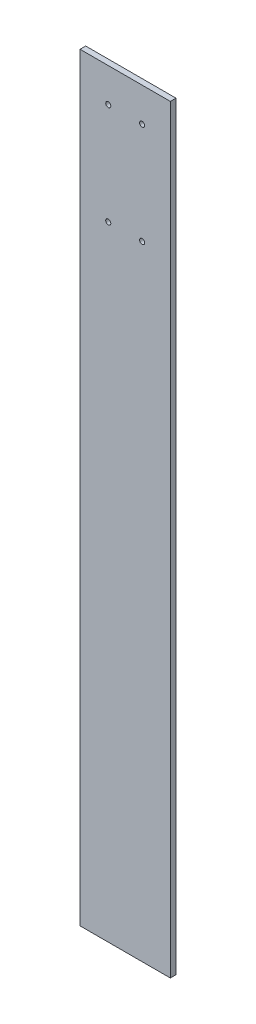
SolidWorks part; units mm, degrees
material "Acrylic (Medium-high impact)"
ref_plane "Front Plane" through (0, 0, 0) normal (0, 0, 1) x (1, 0, 0)
ref_plane "Top Plane" through (0, 0, 0) normal (0, 1, 0) x (1, 0, 0)
ref_plane "Right Plane" through (0, 0, 0) normal (1, 0, 0) x (0, 0, -1)
sketch "Sketch1" plane through (0, 0, 0) normal (0, 1, 0) x (1, 0, 0)
  line L0 (0, 0) -> (0, 76.2) construction
  line L2 (25.4, 68.667) -> (-25.4, 68.667)
  line L3 (25.4, 68.667) -> (25.4, 71.842)
  line L4 (25.4, 71.842) -> (-25.4, 71.842)
  line L5 (-25.4, 68.667) -> (-25.4, 71.842)
  line L6 (25.4, 68.667) -> (-25.4, 71.842) construction
  line L7 (25.4, 71.842) -> (-25.4, 68.667) construction
  circle A0 centre (0, 0) radius 76.2 construction
  point P4 (0, 70.2545)
  dimension "D1" = 152.4
  dimension "D2" = 3.175
  dimension "D3" = 50.8
extrude "Boss-Extrude1" add sketch "Sketch1" along normal blind 427.1518
sketch "Sketch2" plane through (0, 0, -68.667) normal (0, 0, 1) x (1, 0, 0)
  line L1 (-25.4, 427.1518) -> (25.4, 427.1518)
  line L2 (-25.4, 427.1518) -> (-25.4, 0)
  line L3 (-25.4, 0) -> (25.4, 0)
  line L4 (25.4, 427.1518) -> (25.4, 0)
sketch "Sketch3" plane through (0, 0, -68.667) normal (0, 0, 1) x (1, 0, 0)
  line L0 (0, 427.1518) -> (0, 0) construction
  line L1 (-25.4, 427.1518) -> (25.4, 427.1518) construction
  line L2 (-25.4, 0) -> (25.4, 0) construction
  line L3 (-25.4, 213.5759) -> (25.4, 213.5759) construction
  line L4 (-25.4, 427.1518) -> (-25.4, 0) construction
  line L5 (25.4, 427.1518) -> (25.4, 0) construction
  circle A0 centre (-19.05, 376.3518) radius 1.4224
  circle A1 centre (-12.7, 376.3518) radius 1.4224
  circle A2 centre (-6.35, 376.3518) radius 1.4224
  circle A3 centre (0, 376.3518) radius 1.4224
  circle A4 centre (6.35, 376.3518) radius 1.4224
  circle A5 centre (12.7, 376.3518) radius 1.4224
  circle A6 centre (19.05, 376.3518) radius 1.4224
  circle A7 centre (-12.7, 370.0018) radius 1.4224
  circle A8 centre (-6.35, 370.0018) radius 1.4224
  circle A9 centre (0, 370.0018) radius 1.4224
  circle A10 centre (6.35, 370.0018) radius 1.4224
  circle A11 centre (12.7, 370.0018) radius 1.4224
  circle A12 centre (19.05, 370.0018) radius 1.4224
  circle A13 centre (-12.7, 363.6518) radius 1.4224
  circle A14 centre (-6.35, 363.6518) radius 1.4224
  circle A15 centre (0, 363.6518) radius 1.4224
  circle A16 centre (6.35, 363.6518) radius 1.4224
  circle A17 centre (12.7, 363.6518) radius 1.4224
  circle A18 centre (19.05, 363.6518) radius 1.4224
  circle A19 centre (-12.7, 357.3018) radius 1.4224
  circle A20 centre (-6.35, 357.3018) radius 1.4224
  circle A21 centre (0, 357.3018) radius 1.4224
  circle A22 centre (6.35, 357.3018) radius 1.4224
  circle A23 centre (12.7, 357.3018) radius 1.4224
  circle A24 centre (19.05, 357.3018) radius 1.4224
  circle A25 centre (-12.7, 350.9518) radius 1.4224
  circle A26 centre (-6.35, 350.9518) radius 1.4224
  circle A27 centre (0, 350.9518) radius 1.4224
  circle A28 centre (6.35, 350.9518) radius 1.4224
  circle A29 centre (12.7, 350.9518) radius 1.4224
  circle A30 centre (19.05, 350.9518) radius 1.4224
  circle A31 centre (-12.7, 344.6018) radius 1.4224
  circle A32 centre (-6.35, 344.6018) radius 1.4224
  circle A33 centre (0, 344.6018) radius 1.4224
  circle A34 centre (6.35, 344.6018) radius 1.4224
  circle A35 centre (12.7, 344.6018) radius 1.4224
  circle A36 centre (19.05, 344.6018) radius 1.4224
  circle A37 centre (-12.7, 338.2518) radius 1.4224
  circle A38 centre (-6.35, 338.2518) radius 1.4224
  circle A39 centre (0, 338.2518) radius 1.4224
  circle A40 centre (6.35, 338.2518) radius 1.4224
  circle A41 centre (12.7, 338.2518) radius 1.4224
  circle A42 centre (19.05, 338.2518) radius 1.4224
  circle A43 centre (-12.7, 331.9018) radius 1.4224
  circle A44 centre (-6.35, 331.9018) radius 1.4224
  circle A45 centre (0, 331.9018) radius 1.4224
  circle A46 centre (6.35, 331.9018) radius 1.4224
  circle A47 centre (12.7, 331.9018) radius 1.4224
  circle A48 centre (19.05, 331.9018) radius 1.4224
  circle A49 centre (-19.05, 370.0018) radius 1.4224
  circle A50 centre (-19.05, 363.6518) radius 1.4224
  circle A51 centre (-19.05, 357.3018) radius 1.4224
  circle A52 centre (-19.05, 350.9518) radius 1.4224
  circle A53 centre (-19.05, 344.6018) radius 1.4224
  circle A54 centre (-19.05, 338.2518) radius 1.4224
  circle A55 centre (-19.05, 331.9018) radius 1.4224
  circle A56 centre (-19.05, 325.5518) radius 1.4224
  circle A57 centre (-12.7, 325.5518) radius 1.4224
  circle A58 centre (-6.35, 325.5518) radius 1.4224
  circle A59 centre (0, 325.5518) radius 1.4224
  circle A60 centre (6.35, 325.5518) radius 1.4224
  circle A61 centre (12.7, 325.5518) radius 1.4224
  circle A62 centre (19.05, 325.5518) radius 1.4224
  circle A63 centre (-19.05, 319.2018) radius 1.4224
  circle A64 centre (-12.7, 319.2018) radius 1.4224
  circle A65 centre (-6.35, 319.2018) radius 1.4224
  circle A66 centre (0, 319.2018) radius 1.4224
  circle A67 centre (6.35, 319.2018) radius 1.4224
  circle A68 centre (12.7, 319.2018) radius 1.4224
  circle A69 centre (19.05, 319.2018) radius 1.4224
  circle A70 centre (-19.05, 312.8518) radius 1.4224
  circle A71 centre (-12.7, 312.8518) radius 1.4224
  circle A72 centre (-6.35, 312.8518) radius 1.4224
  circle A73 centre (0, 312.8518) radius 1.4224
  circle A74 centre (6.35, 312.8518) radius 1.4224
  circle A75 centre (12.7, 312.8518) radius 1.4224
  circle A76 centre (19.05, 312.8518) radius 1.4224
  circle A77 centre (-19.05, 306.5018) radius 1.4224
  circle A78 centre (-12.7, 306.5018) radius 1.4224
  circle A79 centre (-6.35, 306.5018) radius 1.4224
  circle A80 centre (0, 306.5018) radius 1.4224
  circle A81 centre (6.35, 306.5018) radius 1.4224
  circle A82 centre (12.7, 306.5018) radius 1.4224
  circle A83 centre (19.05, 306.5018) radius 1.4224
  circle A84 centre (-19.05, 300.1518) radius 1.4224
  circle A85 centre (-12.7, 300.1518) radius 1.4224
  circle A86 centre (-6.35, 300.1518) radius 1.4224
  circle A87 centre (0, 300.1518) radius 1.4224
  circle A88 centre (6.35, 300.1518) radius 1.4224
  circle A89 centre (12.7, 300.1518) radius 1.4224
  circle A90 centre (19.05, 300.1518) radius 1.4224
  circle A91 centre (-19.05, 293.8018) radius 1.4224
  circle A92 centre (-12.7, 293.8018) radius 1.4224
  circle A93 centre (-6.35, 293.8018) radius 1.4224
  circle A94 centre (0, 293.8018) radius 1.4224
  circle A95 centre (6.35, 293.8018) radius 1.4224
  circle A96 centre (12.7, 293.8018) radius 1.4224
  circle A97 centre (19.05, 293.8018) radius 1.4224
  circle A98 centre (-19.05, 287.4518) radius 1.4224
  circle A99 centre (-12.7, 287.4518) radius 1.4224
  circle A100 centre (-6.35, 287.4518) radius 1.4224
  circle A101 centre (0, 287.4518) radius 1.4224
  circle A102 centre (6.35, 287.4518) radius 1.4224
  circle A103 centre (12.7, 287.4518) radius 1.4224
  circle A104 centre (19.05, 287.4518) radius 1.4224
  circle A105 centre (19.05, 139.7) radius 1.4224
  circle A106 centre (12.7, 139.7) radius 1.4224
  circle A107 centre (6.35, 139.7) radius 1.4224
  circle A108 centre (0, 139.7) radius 1.4224
  circle A109 centre (-6.35, 139.7) radius 1.4224
  circle A110 centre (-12.7, 139.7) radius 1.4224
  circle A111 centre (-19.05, 139.7) radius 1.4224
  circle A112 centre (19.05, 133.35) radius 1.4224
  circle A113 centre (12.7, 133.35) radius 1.4224
  circle A114 centre (6.35, 133.35) radius 1.4224
  circle A115 centre (0, 133.35) radius 1.4224
  circle A116 centre (-6.35, 133.35) radius 1.4224
  circle A117 centre (-12.7, 133.35) radius 1.4224
  circle A118 centre (-19.05, 133.35) radius 1.4224
  circle A119 centre (19.05, 127) radius 1.4224
  circle A120 centre (12.7, 127) radius 1.4224
  circle A121 centre (6.35, 127) radius 1.4224
  circle A122 centre (0, 127) radius 1.4224
  circle A123 centre (-6.35, 127) radius 1.4224
  circle A124 centre (-12.7, 127) radius 1.4224
  circle A125 centre (-19.05, 127) radius 1.4224
  circle A126 centre (19.05, 120.65) radius 1.4224
  circle A127 centre (12.7, 120.65) radius 1.4224
  circle A128 centre (6.35, 120.65) radius 1.4224
  circle A129 centre (0, 120.65) radius 1.4224
  circle A130 centre (-6.35, 120.65) radius 1.4224
  circle A131 centre (-12.7, 120.65) radius 1.4224
  circle A132 centre (-19.05, 120.65) radius 1.4224
  circle A133 centre (19.05, 114.3) radius 1.4224
  circle A134 centre (12.7, 114.3) radius 1.4224
  circle A135 centre (6.35, 114.3) radius 1.4224
  circle A136 centre (0, 114.3) radius 1.4224
  circle A137 centre (-6.35, 114.3) radius 1.4224
  circle A138 centre (-12.7, 114.3) radius 1.4224
  circle A139 centre (-19.05, 114.3) radius 1.4224
  circle A140 centre (19.05, 107.95) radius 1.4224
  circle A141 centre (12.7, 107.95) radius 1.4224
  circle A142 centre (6.35, 107.95) radius 1.4224
  circle A143 centre (0, 107.95) radius 1.4224
  circle A144 centre (-6.35, 107.95) radius 1.4224
  circle A145 centre (-12.7, 107.95) radius 1.4224
  circle A146 centre (-19.05, 107.95) radius 1.4224
  circle A147 centre (19.05, 101.6) radius 1.4224
  circle A148 centre (12.7, 101.6) radius 1.4224
  circle A149 centre (6.35, 101.6) radius 1.4224
  circle A150 centre (0, 101.6) radius 1.4224
  circle A151 centre (-6.35, 101.6) radius 1.4224
  circle A152 centre (-12.7, 101.6) radius 1.4224
  circle A153 centre (-19.05, 101.6) radius 1.4224
  circle A154 centre (-19.05, 95.25) radius 1.4224
  circle A155 centre (-19.05, 88.9) radius 1.4224
  circle A156 centre (-19.05, 82.55) radius 1.4224
  circle A157 centre (-19.05, 76.2) radius 1.4224
  circle A158 centre (-19.05, 69.85) radius 1.4224
  circle A159 centre (-19.05, 63.5) radius 1.4224
  circle A160 centre (-19.05, 57.15) radius 1.4224
  circle A161 centre (19.05, 95.25) radius 1.4224
  circle A162 centre (12.7, 95.25) radius 1.4224
  circle A163 centre (6.35, 95.25) radius 1.4224
  circle A164 centre (0, 95.25) radius 1.4224
  circle A165 centre (-6.35, 95.25) radius 1.4224
  circle A166 centre (-12.7, 95.25) radius 1.4224
  circle A167 centre (19.05, 88.9) radius 1.4224
  circle A168 centre (12.7, 88.9) radius 1.4224
  circle A169 centre (6.35, 88.9) radius 1.4224
  circle A170 centre (0, 88.9) radius 1.4224
  circle A171 centre (-6.35, 88.9) radius 1.4224
  circle A172 centre (-12.7, 88.9) radius 1.4224
  circle A173 centre (19.05, 82.55) radius 1.4224
  circle A174 centre (12.7, 82.55) radius 1.4224
  circle A175 centre (6.35, 82.55) radius 1.4224
  circle A176 centre (0, 82.55) radius 1.4224
  circle A177 centre (-6.35, 82.55) radius 1.4224
  circle A178 centre (-12.7, 82.55) radius 1.4224
  circle A179 centre (19.05, 76.2) radius 1.4224
  circle A180 centre (12.7, 76.2) radius 1.4224
  circle A181 centre (6.35, 76.2) radius 1.4224
  circle A182 centre (0, 76.2) radius 1.4224
  circle A183 centre (-6.35, 76.2) radius 1.4224
  circle A184 centre (-12.7, 76.2) radius 1.4224
  circle A185 centre (19.05, 69.85) radius 1.4224
  circle A186 centre (12.7, 69.85) radius 1.4224
  circle A187 centre (6.35, 69.85) radius 1.4224
  circle A188 centre (0, 69.85) radius 1.4224
  circle A189 centre (-6.35, 69.85) radius 1.4224
  circle A190 centre (-12.7, 69.85) radius 1.4224
  circle A191 centre (19.05, 63.5) radius 1.4224
  circle A192 centre (12.7, 63.5) radius 1.4224
  circle A193 centre (6.35, 63.5) radius 1.4224
  circle A194 centre (0, 63.5) radius 1.4224
  circle A195 centre (-6.35, 63.5) radius 1.4224
  circle A196 centre (-12.7, 63.5) radius 1.4224
  circle A197 centre (19.05, 57.15) radius 1.4224
  circle A198 centre (12.7, 57.15) radius 1.4224
  circle A199 centre (6.35, 57.15) radius 1.4224
  circle A200 centre (0, 57.15) radius 1.4224
  circle A201 centre (-6.35, 57.15) radius 1.4224
  circle A202 centre (-12.7, 57.15) radius 1.4224
  circle A203 centre (19.05, 50.8) radius 1.4224
  circle A204 centre (12.7, 50.8) radius 1.4224
  circle A205 centre (6.35, 50.8) radius 1.4224
  circle A206 centre (0, 50.8) radius 1.4224
  circle A207 centre (-6.35, 50.8) radius 1.4224
  circle A208 centre (-12.7, 50.8) radius 1.4224
  circle A209 centre (-19.05, 50.8) radius 1.4224
  dimension "D1" = 2.8448
  dimension "D2" = 6.35
  dimension "D3" = 50.8
  dimension "D4" = 7
  dimension "D5" = 8
  dimension "D6" = 8
sketch "Sketch4" plane through (0, 0, -68.667) normal (0, 0, 1) x (1, 0, 0)
  line L0 (0, 427.1518) -> (0, 0) construction
  line L1 (-25.4, 427.1518) -> (25.4, 427.1518) construction
  line L2 (-25.4, 0) -> (25.4, 0) construction
  circle A0 centre (-3.175, 376.3518) radius 1.4224
  circle A2 centre (-9.525, 376.3518) radius 1.4224
  circle A4 centre (-9.525, 370.0018) radius 1.4224
  circle A6 centre (-9.525, 363.6518) radius 1.4224
  circle A8 centre (-9.525, 357.3018) radius 1.4224
  circle A10 centre (-9.525, 350.9518) radius 1.4224
  circle A12 centre (-9.525, 344.6018) radius 1.4224
  circle A14 centre (-9.525, 338.2518) radius 1.4224
  circle A16 centre (-9.525, 331.9018) radius 1.4224
  circle A18 centre (-9.525, 325.5518) radius 1.4224
  circle A20 centre (-9.525, 319.2018) radius 1.4224
  circle A22 centre (-9.525, 312.8518) radius 1.4224
  circle A24 centre (-9.525, 306.5018) radius 1.4224
  circle A26 centre (-9.525, 300.1518) radius 1.4224
  circle A28 centre (-9.525, 293.8018) radius 1.4224
  circle A30 centre (-9.525, 287.4518) radius 1.4224
  circle A32 centre (-9.525, 281.1018) radius 1.4224
  circle A34 centre (-3.175, 370.0018) radius 1.4224
  circle A35 centre (-3.175, 363.6518) radius 1.4224
  circle A36 centre (-3.175, 357.3018) radius 1.4224
  circle A37 centre (-3.175, 350.9518) radius 1.4224
  circle A38 centre (-3.175, 344.6018) radius 1.4224
  circle A39 centre (-3.175, 338.2518) radius 1.4224
  circle A40 centre (-3.175, 331.9018) radius 1.4224
  circle A41 centre (-3.175, 325.5518) radius 1.4224
  circle A42 centre (-3.175, 319.2018) radius 1.4224
  circle A43 centre (-3.175, 312.8518) radius 1.4224
  circle A44 centre (-3.175, 306.5018) radius 1.4224
  circle A45 centre (-3.175, 300.1518) radius 1.4224
  circle A46 centre (-3.175, 293.8018) radius 1.4224
  circle A47 centre (-3.175, 287.4518) radius 1.4224
  circle A48 centre (-3.175, 281.1018) radius 1.4224
  circle A49 centre (3.175, 281.1018) radius 1.4224
  circle A50 centre (3.175, 287.4518) radius 1.4224
  circle A51 centre (3.175, 293.8018) radius 1.4224
  circle A52 centre (3.175, 300.1518) radius 1.4224
  circle A53 centre (3.175, 306.5018) radius 1.4224
  circle A54 centre (3.175, 312.8518) radius 1.4224
  circle A55 centre (3.175, 319.2018) radius 1.4224
  circle A56 centre (3.175, 325.5518) radius 1.4224
  circle A57 centre (3.175, 331.9018) radius 1.4224
  circle A58 centre (3.175, 338.2518) radius 1.4224
  circle A59 centre (3.175, 344.6018) radius 1.4224
  circle A60 centre (3.175, 350.9518) radius 1.4224
  circle A61 centre (3.175, 357.3018) radius 1.4224
  circle A62 centre (3.175, 363.6518) radius 1.4224
  circle A63 centre (3.175, 370.0018) radius 1.4224
  circle A65 centre (9.525, 281.1018) radius 1.4224
  circle A67 centre (9.525, 287.4518) radius 1.4224
  circle A69 centre (9.525, 293.8018) radius 1.4224
  circle A71 centre (9.525, 300.1518) radius 1.4224
  circle A73 centre (9.525, 306.5018) radius 1.4224
  circle A75 centre (9.525, 312.8518) radius 1.4224
  circle A77 centre (9.525, 319.2018) radius 1.4224
  circle A79 centre (9.525, 325.5518) radius 1.4224
  circle A81 centre (9.525, 331.9018) radius 1.4224
  circle A83 centre (9.525, 338.2518) radius 1.4224
  circle A85 centre (9.525, 344.6018) radius 1.4224
  circle A87 centre (9.525, 350.9518) radius 1.4224
  circle A89 centre (9.525, 357.3018) radius 1.4224
  circle A91 centre (9.525, 363.6518) radius 1.4224
  circle A93 centre (9.525, 370.0018) radius 1.4224
  circle A95 centre (9.525, 376.3518) radius 1.4224
  circle A96 centre (3.175, 376.3518) radius 1.4224
  circle A97 centre (-9.525, 382.7018) radius 1.4224
  circle A100 centre (9.525, 382.7018) radius 1.4224
  circle A103 centre (-9.525, 389.0518) radius 1.4224
  circle A106 centre (9.525, 389.0518) radius 1.4224
  circle A109 centre (-9.525, 395.4018) radius 1.4224
  circle A112 centre (9.525, 395.4018) radius 1.4224
  circle A115 centre (-9.525, 401.7518) radius 1.4224
  circle A118 centre (9.525, 401.7518) radius 1.4224
  circle A121 centre (-9.525, 408.1018) radius 1.4224
  circle A124 centre (9.525, 408.1018) radius 1.4224
  circle A127 centre (-9.525, 414.4518) radius 1.4224
  circle A130 centre (9.525, 414.4518) radius 1.4224
  circle A144 centre (-3.175, 382.7018) radius 1.4224 [skipped]
  circle A145 centre (-3.175, 389.0518) radius 1.4224 [skipped]
  circle A146 centre (-3.175, 395.4018) radius 1.4224 [skipped]
  circle A147 centre (-3.175, 401.7518) radius 1.4224 [skipped]
  circle A148 centre (-3.175, 408.1018) radius 1.4224 [skipped]
  circle A149 centre (-3.175, 414.4518) radius 1.4224 [skipped]
  circle A150 centre (3.175, 382.7018) radius 1.4224 [skipped]
  circle A151 centre (3.175, 389.0518) radius 1.4224 [skipped]
  circle A152 centre (3.175, 395.4018) radius 1.4224 [skipped]
  circle A153 centre (3.175, 401.7518) radius 1.4224 [skipped]
  circle A154 centre (3.175, 408.1018) radius 1.4224 [skipped]
  circle A155 centre (3.175, 414.4518) radius 1.4224 [skipped]
  circle A156 centre (-15.875, 363.6518) radius 1.4224 [skipped]
  circle A157 centre (-15.875, 357.3018) radius 1.4224 [skipped]
  circle A158 centre (-15.875, 350.9518) radius 1.4224 [skipped]
  circle A159 centre (-15.875, 344.6018) radius 1.4224 [skipped]
  circle A160 centre (-15.875, 338.2518) radius 1.4224 [skipped]
  circle A161 centre (-15.875, 331.9018) radius 1.4224 [skipped]
  circle A162 centre (-15.875, 325.5518) radius 1.4224 [skipped]
  circle A163 centre (-15.875, 319.2018) radius 1.4224 [skipped]
  circle A164 centre (-15.875, 312.8518) radius 1.4224 [skipped]
  circle A165 centre (-15.875, 306.5018) radius 1.4224 [skipped]
  circle A166 centre (-15.875, 300.1518) radius 1.4224 [skipped]
  circle A167 centre (-15.875, 293.8018) radius 1.4224 [skipped]
  circle A168 centre (-15.875, 287.4518) radius 1.4224 [skipped]
  circle A169 centre (-15.875, 281.1018) radius 1.4224 [skipped]
  circle A170 centre (-15.875, 376.3518) radius 1.4224 [skipped]
  circle A171 centre (-15.875, 370.0018) radius 1.4224 [skipped]
  dimension "D2" = 2.8448
  dimension "D1" = 3.175
  dimension "D3" = 50.8
  dimension "D4" = 3
  dimension "D5" = 16
  dimension "D7" = 7
extrude "Cut-Extrude2" cut sketch "Sketch4" against normal blind 2.54
sketch "Sketch5" plane through (0, 0, -68.667) normal (0, 0, 1) x (1, 0, 0)
  line L1 (-6.4666, 378.8778) -> (6.1161, 378.8778)
  line L2 (-6.4666, 378.8778) -> (-6.4666, 277.848)
  line L3 (-6.4666, 277.848) -> (6.1161, 277.848)
  line L4 (6.1161, 378.8778) -> (6.1161, 277.848)
extrude "Boss-Extrude2" add sketch "Sketch5" against normal blind 2.54
sketch "Sketch6" plane through (0, 0, -68.667) normal (0, 0, 1) x (1, 0, 0)
  line L1 (-20.2574, 381.0412) -> (-12.7108, 381.0412)
  line L2 (-20.2574, 381.0412) -> (-20.2574, 272.3701)
  line L3 (-20.2574, 272.3701) -> (-12.7108, 272.3701)
  line L4 (-12.7108, 381.0412) -> (-12.7108, 272.3701)
  line L5 (12.4446, 381.0412) -> (21.5005, 381.0412)
  line L6 (12.4446, 381.0412) -> (12.4446, 272.3701)
  line L7 (12.4446, 272.3701) -> (21.5005, 272.3701)
  line L8 (21.5005, 381.0412) -> (21.5005, 272.3701)
extrude "Boss-Extrude3" add sketch "Sketch6" against normal blind 2.54
sketch "Sketch7" plane through (0, 0, -68.667) normal (0, 0, 1) x (1, 0, 0)
  line L0 (25.4, 427.1518) -> (25.4, 0) construction
  line L1 (-25.4, 427.1518) -> (25.4, 427.1518)
  line L2 (-25.4, 427.1518) -> (-25.4, 410.6418)
  line L3 (-25.4, 410.6418) -> (25.4, 410.6418)
  line L4 (25.4, 427.1518) -> (25.4, 410.6418)
  dimension "D1" = 16.51
extrude "Boss-Extrude4" add sketch "Sketch7" against normal blind 3.175
sketch "Sketch8" plane through (0, 0, -68.667) normal (0, 0, 1) x (1, 0, 0)
  line L0 (-25.4, 427.1518) -> (-25.4, 0) construction
  line L1 (-25.4, 404.9269) -> (25.4, 404.9269)
  line L2 (-25.4, 404.9269) -> (-25.4, 353.7389)
  line L3 (-25.4, 353.7389) -> (25.4, 353.7389)
  line L4 (25.4, 404.9269) -> (25.4, 353.7389)
  line L5 (25.4, 427.1518) -> (25.4, 0) construction
extrude "Boss-Extrude5" add sketch "Sketch8" against normal blind 3.175
sketch "Sketch9" plane through (0, 0, -68.667) normal (0, 0, 1) x (1, 0, 0)
  line L0 (-25.4, 427.1518) -> (-25.4, 0) construction
  line L1 (-25.4, 347.6) -> (25.4, 347.6)
  line L2 (-25.4, 347.6) -> (-25.4, 277.4309)
  line L3 (-25.4, 277.4309) -> (25.4, 277.4309)
  line L4 (25.4, 347.6) -> (25.4, 277.4309)
  line L5 (25.4, 427.1518) -> (25.4, 0) construction
extrude "Boss-Extrude6" add sketch "Sketch9" against normal blind 3.175
